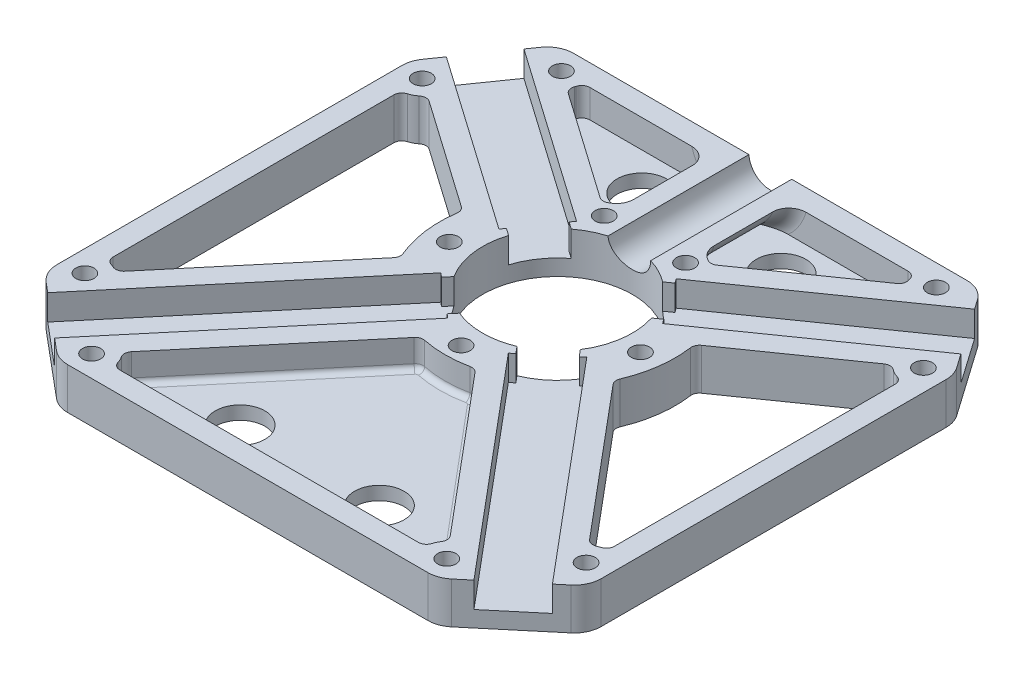
SolidWorks part; units mm, degrees
ref_plane "Front" through (0, 0, 0) normal (0, 0, 1) x (1, 0, 0)
ref_plane "Top" through (0, 0, 0) normal (0, 1, 0) x (1, 0, 0)
ref_plane "Right" through (0, 0, 0) normal (1, 0, 0) x (0, 0, -1)
sketch "Layout Sketch" plane through (0, 0, 0) normal (0, 1, 0) x (1, 0, 0)
  line L0 (0, 0) -> (0, 215) construction
  line L1 (0, 0) -> (-176.1177, 123.3189) construction
  line L2 (0, 0) -> (-138.1993, -164.6996) construction
  line L3 (-176.1177, 123.3189) -> (-12.2873, 8.6036)
  line L4 (-138.1993, -164.6996) -> (-9.6418, -11.4907)
  line L5 (138.1993, -164.6996) -> (9.6418, -11.4907)
  line L6 (176.1177, 123.3189) -> (12.2873, 8.6036)
  line L8 (-43.5, 110) -> (43.5, 110)
  line L9 (-43.5, 110) -> (-43.5, -70)
  line L10 (-43.5, -70) -> (43.5, -70)
  line L11 (43.5, 110) -> (43.5, -70)
  line L12 (-43.5, 110) -> (43.5, -70) construction
  line L13 (-43.5, -70) -> (43.5, 110) construction
  circle A0 centre (0, 0) radius 215
  circle A1 centre (0, 0) radius 15
  circle A2 centre (-176.1177, 123.3189) radius 127
  circle A3 centre (-138.1993, -164.6996) radius 127
  circle A4 centre (138.1993, -164.6996) radius 127
  circle A5 centre (176.1177, 123.3189) radius 127
  point P17 (0, 20)
  dimension "D3" = 30
  dimension "D5" = 430
  dimension "D6" = 254
  dimension "D1" = 55
  dimension "D2" = 40
  dimension "D4" = 200
  dimension "D7" = 87
  dimension "D8" = 70
  dimension "D9" = 180
ref_plane "Plane1" through (12.2873, 0, -8.6036) normal (-0.8192, 0, 0.5736) x (0.5736, 0, 0.8192)
sketch "Sketch2" plane through (12.2873, 0, -8.6036) normal (-0.8192, 0, 0.5736) x (0.5736, 0, 0.8192)
  line L1 (-5, -5) -> (5, -5)
  line L2 (-5, -5) -> (-5, 5)
  line L3 (-5, 5) -> (5, 5)
  line L4 (5, -5) -> (5, 5)
  line L5 (-5, -5) -> (5, 5) construction
  line L6 (-5, 5) -> (5, -5) construction
  circle A0 centre (0, 0) radius 4
  dimension "D2" = 8
  dimension "D1" = 10
extrude "Boss-Extrude2" add sketch "Sketch2" against normal up to vertex (200 mm away) contours L3 L4 L1 L2 up to point (176.1177, 0, -123.3189)
ref_plane "Plane2" through (9.6418, 0, 11.4907) normal (-0.6428, 0, -0.766) x (-0.766, 0, 0.6428)
sketch "Sketch4" plane through (9.6418, 0, 11.4907) normal (-0.6428, 0, -0.766) x (-0.766, 0, 0.6428)
  line B0 (-5, -5) -> (5, -5)
  line B1 (-5, -5) -> (-5, 5)
  line B2 (-5, 5) -> (5, 5)
  line B3 (5, -5) -> (5, 5)
  circle B4 centre (0, 0) radius 4
sketch_block_instance "Block-10mm Carbon-1"
sketch_block "Block-10mm Carbon" parameters "D2"=8, "D1"=10
extrude "Boss-Extrude1" add sketch "Sketch4" against normal up to vertex (200 mm away) separate body up to point (138.1993, 0, 164.6996)
mirror "Mirror1" about plane through (0, 0, 0) normal (1, 0, 0) of bodies 103 102
sketch "Sketch5" plane through (0, -5, 0) normal (0, -1, 0) x (1, 0, 0)
  line L0 (-39.3176, -39.7382) -> (39.3176, -39.7382)
  line L1 (39.3176, -39.7382) -> (50.7891, -23.3552)
  line L2 (50.7891, -23.3552) -> (50.7891, 44.9709)
  line L3 (50.7891, 44.9709) -> (35.4682, 57.8266)
  line L4 (35.4682, 57.8266) -> (-35.4682, 57.8266)
  line L5 (0, 57.8266) -> (0, -39.7382) construction
  line L6 (-39.3176, -39.7382) -> (-50.7891, -23.3552)
  line L7 (-50.7891, -23.3552) -> (-50.7891, 44.9709)
  line L8 (-50.7891, 44.9709) -> (-35.4682, 57.8266)
  line L9 (9.6418, 11.4907) -> (138.1993, 164.6996) construction
  line L10 (13.472, 8.2767) -> (5.8116, 14.7046) construction
  line L11 (142.0296, 161.4856) -> (134.3691, 167.9135) construction
  line L12 (12.2873, -8.6036) -> (176.1177, -123.3189) construction
  line L13 (9.4194, -12.6994) -> (15.1552, -4.5079) construction
  line L14 (173.2498, -127.4147) -> (178.9856, -119.2232) construction
  point P23 (45.0534, -31.5467)
  point P24 (43.1287, 51.3988)
  dimension "D1" = 20
  dimension "D2" = 40
  dimension "D3" = 101.5783
extrude "Boss-Extrude3" add sketch "Sketch5" along normal blind 3 and the other way blind 4.75 separate body
sketch "Sketch7" plane through (0, -5, 0) normal (0, -1, 0) x (1, 0, 0)
  line L0 (5.6584, 14.8332) -> (39.1453, 54.7413)
  line L1 (5.6584, 14.8332) -> (13.6252, 8.1482)
  line L2 (39.1453, 54.7413) -> (47.1121, 48.0563)
  line L3 (42.0708, -35.8063) -> (9.3047, -12.8632)
  line L4 (42.0708, -35.8063) -> (48.036, -27.2871)
  line L5 (9.3047, -12.8632) -> (15.2699, -4.3441)
  line L6 (48.036, -27.2871) -> (15.2699, -4.3441)
  line L7 (42.0708, -35.8063) -> (15.2699, -4.3441) construction
  line L8 (9.3047, -12.8632) -> (48.036, -27.2871) construction
  line L9 (9.4194, -12.6994) -> (15.1552, -4.5079) construction
  line L10 (176.1177, -123.3189) -> (12.2873, -8.6036) construction
  line L11 (173.2498, -127.4147) -> (178.9856, -119.2232) construction
  line L12 (39.3176, -39.7382) -> (50.7891, -23.3552) construction
  line L13 (173.2498, -127.4147) -> (9.4194, -12.6994) construction
  line L14 (9.6418, 11.4907) -> (138.1993, 164.6996) construction
  line L15 (5.8116, 14.7046) -> (13.472, 8.2767) construction
  line L16 (134.3691, 167.9135) -> (142.0296, 161.4856) construction
  line L17 (13.6252, 8.1482) -> (47.1121, 48.0563)
  line L18 (5.6584, 14.8332) -> (47.1121, 48.0563) construction
  line L19 (39.1453, 54.7413) -> (13.6252, 8.1482) construction
  line L20 (50.7891, 44.9709) -> (35.4682, 57.8266) construction
  line L21 (142.0296, 161.4856) -> (13.472, 8.2767) construction
  line L22 (0, 0) -> (0, 57.8266) construction
  line L23 (35.4682, 57.8266) -> (-35.4682, 57.8266) construction
  line L24 (-39.1453, 54.7413) -> (-47.1121, 48.0563)
  line L25 (-5.6584, 14.8332) -> (-39.1453, 54.7413)
  line L26 (-13.6252, 8.1482) -> (-47.1121, 48.0563)
  line L27 (-5.6584, 14.8332) -> (-13.6252, 8.1482)
  line L28 (-48.036, -27.2871) -> (-15.2699, -4.3441)
  line L29 (-42.0708, -35.8063) -> (-48.036, -27.2871)
  line L30 (-42.0708, -35.8063) -> (-9.3047, -12.8632)
  line L31 (-9.3047, -12.8632) -> (-15.2699, -4.3441)
  point P5 (28.6703, -20.0752)
  point P22 (26.3852, 31.4447)
  dimension "D1" = 0.2
  dimension "D2" = 0.2
extrude "Cut-Extrude1" cut sketch "Sketch7" against normal through all
sketch "Sketch8" plane through (0, -0.25, 0) normal (0, 1, 0) x (1, 0, 0)
  line L0 (-9.8783, 12.0441) -> (-8.5309, 11.1006)
  line L1 (-9.3047, 12.8632) -> (-15.2699, 4.3441) construction
  line L2 (-14.6963, 5.1632) -> (-13.3489, 4.2198)
  line L3 (-9.3047, 12.8632) -> (-15.2699, 4.3441) construction
  line L4 (-12.8592, -8.791) -> (-11.8019, -7.5309)
  line L5 (-13.6252, -8.1482) -> (-5.6584, -14.8332) construction
  line L6 (-6.4244, -14.1904) -> (-5.3671, -12.9303)
  line L7 (-13.6252, -8.1482) -> (-5.6584, -14.8332) construction
  line L8 (-5.6584, -14.8332) -> (-39.1453, -54.7413) construction
  line L9 (-47.1121, -48.0563) -> (-13.6252, -8.1482) construction
  line L10 (-15.2699, 4.3441) -> (-48.036, 27.2871) construction
  line L11 (-42.0708, 35.8063) -> (-9.3047, 12.8632) construction
  line L12 (0, 0) -> (0, 39.7382) construction
  line L13 (-39.3176, 39.7382) -> (39.3176, 39.7382) construction
  line L14 (6.4244, -14.1904) -> (5.3671, -12.9303)
  line L15 (12.8592, -8.791) -> (11.8019, -7.5309)
  line L16 (14.6963, 5.1632) -> (13.3489, 4.2198)
  line L17 (9.8783, 12.0441) -> (8.5309, 11.1006)
  line L18 (15.2699, 4.3441) -> (9.3047, 12.8632) construction
  line L19 (5.6584, -14.8332) -> (13.6252, -8.1482) construction
  line L20 (14.6963, 5.1632) -> (9.8783, 12.0441)
  line L21 (-9.8783, 12.0441) -> (-14.6963, 5.1632)
  line L22 (-12.8592, -8.791) -> (-6.4244, -14.1904)
  line L23 (6.4244, -14.1904) -> (12.8592, -8.791)
  arc A0 (-13.3489, 4.2198) -> (-11.8019, -7.5309) centre (0, 0) ccw
  arc A1 (-5.3671, -12.9303) -> (5.3671, -12.9303) centre (0, 0) ccw
  arc A2 (11.8019, -7.5309) -> (13.3489, 4.2198) centre (0, 0) ccw
  arc A3 (8.5309, 11.1006) -> (-8.5309, 11.1006) centre (0, 0) ccw
  dimension "D5" = 28
  dimension "D1" = 1
  dimension "D2" = 1
  dimension "D3" = 1
  dimension "D4" = 1
extrude "Cut-Extrude2" cut sketch "Sketch8" against normal up to surface (4.75 mm away) up to face at (28.6703, -5, -20.0752)
sketch "Sketch14" plane through (0, -0.25, 0) normal (0, 1, 0) x (1, 0, 0)
  line L0 (17.9502, 1.3378) -> (43.5125, 19.2367)
  line L1 (46.7891, 17.531) -> (46.7891, -37.4485)
  line L2 (44.218, -38.3843) -> (16.9923, -5.938)
  line L3 (2.8971, -17.7653) -> (30.585, -50.7625)
  line L4 (31.7232, 33.4439) -> (7.3964, 16.4102)
  line L27 (7.3964, 16.4102) -> (34.9998, 35.7382)
  line L28 (34.9998, 35.7382) -> (-34.9998, 35.7382)
  line L29 (-34.9998, 35.7382) -> (-7.3964, 16.4102)
  line L31 (30.9998, 35.7382) -> (-30.9998, 35.7382)
  line L32 (-31.7232, 33.4439) -> (-7.3964, 16.4102)
  line L33 (-17.9502, 1.3378) -> (-46.7891, 21.531)
  line L34 (-46.7891, 21.531) -> (-46.7891, -41.4485)
  line L35 (-46.7891, -41.4485) -> (-16.9923, -5.938)
  line L36 (-17.9502, 1.3378) -> (-43.5125, 19.2367)
  line L37 (-46.7891, 17.531) -> (-46.7891, -37.4485)
  line L38 (-44.218, -38.3843) -> (-16.9923, -5.938)
  line L39 (0, 0) -> (0, 39.7382) construction
  line L40 (-39.3176, 39.7382) -> (39.3176, 39.7382) construction
  line L41 (0, 0) -> (0, -57.8266) construction
  line L42 (35.4682, -57.8266) -> (-35.4682, -57.8266) construction
  line L48 (-2.8971, -17.7653) -> (-33.1562, -53.8266)
  line L49 (-33.1562, -53.8266) -> (33.1562, -53.8266)
  line L50 (33.1562, -53.8266) -> (2.8971, -17.7653)
  line L51 (-2.8971, -17.7653) -> (-30.585, -50.7625)
  line L52 (-29.1562, -53.8266) -> (29.1562, -53.8266)
  arc A0 (17.9502, 1.3378) -> (16.9923, -5.938) centre (0, 0) cw
  arc A1 (46.7891, 17.531) -> (43.5125, 19.2367) centre (46.7891, 21.531) cw
  arc A2 (44.218, -38.3843) -> (46.7891, -37.4485) centre (46.7891, -41.4485) cw
  arc A3 (7.3964, 16.4102) -> (-7.3964, 16.4102) centre (0, 0) ccw
  arc A4 (7.3964, 16.4102) -> (-7.3964, 16.4102) centre (0, 0) ccw
  arc A5 (-17.9502, 1.3378) -> (-16.9923, -5.938) centre (0, 0) ccw
  arc A6 (-17.9502, 1.3378) -> (-16.9923, -5.938) centre (0, 0) ccw
  arc A7 (-44.218, -38.3843) -> (-46.7891, -37.4485) centre (-46.7891, -41.4485) ccw
  arc A8 (-2.8971, -17.7653) -> (2.8971, -17.7653) centre (0, 0) ccw
  arc A9 (-2.8971, -17.7653) -> (2.8971, -17.7653) centre (0, 0) ccw
  arc A10 (-46.7891, 17.531) -> (-43.5125, 19.2367) centre (-46.7891, 21.531) ccw
  arc A11 (-31.7232, 33.4439) -> (-30.9998, 35.7382) centre (-34.9998, 35.7382) ccw
  arc A12 (-29.1562, -53.8266) -> (-30.585, -50.7625) centre (-33.1562, -53.8266) ccw
  arc A13 (29.1562, -53.8266) -> (30.585, -50.7625) centre (33.1562, -53.8266) cw
  arc A14 (31.7232, 33.4439) -> (30.9998, 35.7382) centre (34.9998, 35.7382) cw
  point P42 (0, -53.8266)
  point P43 (0, 35.7382)
  dimension "D4" = 8
  dimension "D1" = 4
  dimension "D2" = 4
  dimension "D3" = 4
extrude "Cut-Extrude4" cut sketch "Sketch14" against normal offset from surface (5.25 mm away) 2.5 up to face at (0, -8, 9.926)
other "Move Face1" face at (17.6586, -2.875, 2.3248) face at (-17.6586, -2.875, 2.3248) offset 4 parameters "D1"=4
sketch "Sketch15" plane through (0, -0.25, 0) normal (0, 1, 0) x (1, 0, 0)
  line L0 (-44.218, -38.3843) -> (-19.8931, -9.395) construction
  line L1 (-21.6468, 3.9261) -> (-43.5125, 19.2367) construction
  line L3 (-31.7232, 33.4439) -> (-7.3964, 16.4102) construction
  line L4 (7.3964, 16.4102) -> (31.7232, 33.4439) construction
  line L7 (30.585, -50.7625) -> (2.8971, -17.7653) construction
  line L8 (-2.8971, -17.7653) -> (-30.585, -50.7625) construction
  line L9 (19.8931, -9.395) -> (44.218, -38.3843) construction
  line L11 (43.5125, 19.2367) -> (21.6468, 3.9261) construction
  line L12 (-19.1818, -8.5474) -> (-19.8931, -9.395)
  line L13 (-21.6468, 3.9261) -> (-20.7404, 3.2915)
  line L15 (-10.1866, 18.3639) -> (-7.3964, 16.4102)
  line L16 (7.3964, 16.4102) -> (10.1866, 18.3639)
  line L19 (5.0866, -20.3746) -> (2.8971, -17.7653)
  line L20 (-2.8971, -17.7653) -> (-5.0866, -20.3746)
  line L21 (19.8931, -9.395) -> (19.1818, -8.5474)
  line L23 (20.7404, 3.2915) -> (21.6468, 3.9261)
  arc A0 (-20.7404, 3.2915) -> (-19.1818, -8.5474) centre (0, 0) ccw
  arc A2 (8.5309, 11.1006) -> (-8.5309, 11.1006) centre (0, 0) ccw construction
  arc A4 (-21.6468, 3.9261) -> (-19.8931, -9.395) centre (0, 0) ccw construction
  arc A7 (7.3964, 16.4102) -> (-7.3964, 16.4102) centre (0, 0) ccw construction
  arc A11 (-2.8971, -17.7653) -> (2.8971, -17.7653) centre (0, 0) ccw construction
  arc A12 (19.8931, -9.395) -> (21.6468, 3.9261) centre (0, 0) ccw construction
  arc A16 (-21.6468, 3.9261) -> (-19.8931, -9.395) centre (0, 0) ccw
  arc A19 (7.3964, 16.4102) -> (-7.3964, 16.4102) centre (0, 0) ccw
  arc A23 (-2.8971, -17.7653) -> (2.8971, -17.7653) centre (0, 0) ccw
  arc A24 (19.8931, -9.395) -> (21.6468, 3.9261) centre (0, 0) ccw
  arc A27 (10.1866, 18.3639) -> (-10.1866, 18.3639) centre (0, 0) ccw
  arc A28 (19.1818, -8.5474) -> (20.7404, 3.2915) centre (0, 0) ccw
  arc A29 (-5.0866, -20.3746) -> (5.0866, -20.3746) centre (0, 0) ccw
  dimension "D1" = 7
extrude "Boss-Extrude7" add sketch "Sketch15" against normal up to surface (5.25 mm away) up to face at (-37.2665, -5.5, 7.4742)
sketch "Sketch10" plane through (0, 0, -39.7382) normal (0, 0, 1) x (1, 0, 0)
  line L2 (7.5, -0.25) -> (-7.5, -0.25)
  line L3 (35.4682, -0.25) -> (-35.4682, -0.25) construction
  line L4 (0, -0.25) -> (0, 2.875) construction
  arc A0 (-7.5, -0.25) -> (7.5, -0.25) centre (0, 2.875) ccw
  point P4 (-7.5, -0.25)
  point P6 (7.5, -0.25)
  point P12 (0, -5.25)
  dimension "D1" = 15
  dimension "D2" = 5
extrude "Boss-Extrude8" add sketch "Sketch10" along normal up to surface (20.1232 mm away) up to face at (0, -2.875, -19.6819)
sketch "Sketch11" plane through (0, 0, -39.7382) normal (0, 0, -1) x (-1, 0, 0)
  circle A0 centre (0, 0) radius 4
  dimension "D1" = 8
extrude "Cut-Extrude3" cut sketch "Sketch11" against normal up to surface (26.3218 mm away) up to face at (0, -2.625, -12.5503)
hole_wizard "M3 Clearance Hole2" positions "Sketch17" profile "Sketch16" hole size "M3" standard "ANSI Metric" end condition through all
sketch "Sketch17" plane through (0, -0.25, 0) normal (0, 1, 0) x (1, 0, 0)
  line L0 (-21.8118, -2.8716) -> (-13.8802, -1.8274) construction
  line L1 (-10.1866, 18.3639) -> (-7.5, 19.615) construction
  line L4 (-8.8433, 18.9895) -> (-5.9103, 12.6913) construction
  line L7 (0, 0) -> (0, 33.2482) construction
  line L10 (8.8433, 18.9895) -> (5.9103, 12.6913) construction
  circle A0 centre (0, 0) radius 18
  arc A2 (-13.3489, 4.2198) -> (-11.8019, -7.5309) centre (0, 0) ccw construction
  arc A3 (-3.9922, 13.4187) -> (-8.5309, 11.1006) centre (0, 0) ccw construction
  arc A4 (-21.6468, 3.9261) -> (-19.8931, -9.395) centre (0, 0) ccw construction
  point P18 (-46.7891, 21.531)
  point P21 (-34.9998, 35.7382)
  point P24 (-46.7891, -41.4485)
  point P27 (-33.1562, -53.8266)
  point P30 (0, -18)
  point P33 (-17.846, -2.3495)
  point P34 (-7.5989, 16.3174)
  point P60 (33.1562, -53.8266)
  point P63 (17.846, -2.3495)
  point P64 (46.7891, -41.4485)
  point P65 (46.7891, 21.531)
  point P66 (34.9998, 35.7382)
  point P67 (7.5989, 16.3174)
sketch "Sketch16" plane through (-46.7891, -0.25, -21.531) normal (1, 0, 0) x (0, 0, 1)
  line L0 (0, 0) -> (0, 7.75)
  line L1 (0, 7.75) -> (1.7, 7.75)
  line L2 (1.7, 7.75) -> (1.7, 0)
  line L5 (1.7, 0) -> (0, 0)
  line L11 (0, -6.35) -> (0, 107.95) construction
  dimension "Thru Hole Dia." = 3.4
  dimension "Thru Hole Depth" = 7.75
fillet "Fillet1" radius 1.5 24 edges at (46.7891, -2.875, 37.4485) (44.218, -2.875, 38.3843) (-10.1866, -2.875, -18.3639) (10.1866, -2.875, -18.3639) (43.5125, -2.875, -19.2367) (46.7891, -2.875, -17.531) (30.9998, -2.875, -35.7382) (31.7232, -2.875, -33.4439) (-31.7232, -2.875, -33.4439) (-30.9998, -2.875, -35.7382) (29.1562, -2.875, 53.8266) (30.585, -2.875, 50.7625) (5.0866, -2.875, 20.3746) (-5.0866, -2.875, 20.3746) (-29.1562, -2.875, 53.8266) (-30.585, -2.875, 50.7625) (-46.7891, -2.875, 37.4485) (-44.218, -2.875, 38.3843) (-46.7891, -2.875, -17.531) (-43.5125, -2.875, -19.2367) (21.6468, -2.875, -3.9261) (19.8931, -2.875, 9.395) (-19.8931, -2.875, 9.395) (-21.6468, -2.875, -3.9261)
sketch "Sketch18" plane through (0, -5.5, 0) normal (0, 1, 0) x (1, 0, 0)
  line L3 (-46.7891, 16.2395) -> (-46.7891, -36.1569)
  line L4 (-43.3878, -37.3949) -> (-20.4965, -10.1141)
  line L5 (-22.4158, 4.4646) -> (-42.4546, 18.4959)
  line L6 (-46.7891, 16.2395) -> (-46.7891, -36.1569)
  line L7 (-43.3878, -37.3949) -> (-20.4965, -10.1141)
  line L8 (-22.4158, 4.4646) -> (-42.4546, 18.4959)
  line L9 (46.7891, -36.1569) -> (46.7891, 16.2395)
  line L10 (42.4546, 18.4959) -> (22.4158, 4.4646)
  line L11 (20.4965, -10.1141) -> (43.3878, -37.3949)
  line L12 (46.7891, -36.1569) -> (46.7891, 16.2395)
  line L13 (42.4546, 18.4959) -> (22.4158, 4.4646)
  line L14 (20.4965, -10.1141) -> (43.3878, -37.3949)
  arc A7 (-21.7904, 3.0293) -> (-20.2639, -8.5659) centre (0, 0) ccw
  arc A8 (-21.7904, 3.0293) -> (-20.2639, -8.5659) centre (0, 0) ccw
  arc A9 (-46.7891, -36.1569) -> (-45.6982, -37.6001) centre (-45.2891, -36.1569) ccw
  arc A10 (-45.1511, -37.7992) -> (-45.6982, -37.6001) centre (-46.7891, -41.4485) ccw
  arc A11 (-45.1511, -37.7992) -> (-43.3878, -37.3949) centre (-44.5369, -36.4307) ccw
  arc A12 (20.2639, -8.5659) -> (21.7904, 3.0293) centre (0, 0) ccw
  arc A13 (20.2639, -8.5659) -> (21.7904, 3.0293) centre (0, 0) ccw
  arc A15 (-42.4546, 18.4959) -> (-44.2625, 18.43) centre (-43.3149, 17.2672) ccw
  arc A16 (-45.6982, 17.6826) -> (-44.2625, 18.43) centre (-46.7891, 21.531) ccw
  arc A17 (-45.6982, 17.6826) -> (-46.7891, 16.2395) centre (-45.2891, 16.2395) ccw
  arc A18 (-46.7891, -36.1569) -> (-45.6982, -37.6001) centre (-45.2891, -36.1569) ccw
  arc A19 (-45.1511, -37.7992) -> (-45.6982, -37.6001) centre (-46.7891, -41.4485) ccw
  arc A20 (-45.1511, -37.7992) -> (-43.3878, -37.3949) centre (-44.5369, -36.4307) ccw
  arc A22 (-20.4965, -10.1141) -> (-20.2639, -8.5659) centre (-21.6455, -9.1499) ccw
  arc A23 (-20.4965, -10.1141) -> (-20.2639, -8.5659) centre (-21.6455, -9.1499) ccw
  arc A24 (-42.4546, 18.4959) -> (-44.2625, 18.43) centre (-43.3149, 17.2672) ccw
  arc A25 (-45.6982, 17.6826) -> (-44.2625, 18.43) centre (-46.7891, 21.531) ccw
  arc A26 (-45.6982, 17.6826) -> (-46.7891, 16.2395) centre (-45.2891, 16.2395) ccw
  arc A27 (45.6982, -37.6001) -> (45.1511, -37.7992) centre (46.7891, -41.4485) ccw
  arc A28 (45.6982, -37.6001) -> (46.7891, -36.1569) centre (45.2891, -36.1569) ccw
  arc A29 (46.7891, 16.2395) -> (45.6982, 17.6826) centre (45.2891, 16.2395) ccw
  arc A30 (44.2625, 18.43) -> (45.6982, 17.6826) centre (46.7891, 21.531) ccw
  arc A31 (44.2625, 18.43) -> (42.4546, 18.4959) centre (43.3149, 17.2672) ccw
  arc A32 (-21.7904, 3.0293) -> (-22.4158, 4.4646) centre (-23.2762, 3.2358) ccw
  arc A33 (-21.7904, 3.0293) -> (-22.4158, 4.4646) centre (-23.2762, 3.2358) ccw
  arc A34 (22.4158, 4.4646) -> (21.7904, 3.0293) centre (23.2762, 3.2358) ccw
  arc A35 (43.3878, -37.3949) -> (45.1511, -37.7992) centre (44.5369, -36.4307) ccw
  arc A36 (45.6982, -37.6001) -> (45.1511, -37.7992) centre (46.7891, -41.4485) ccw
  arc A37 (45.6982, -37.6001) -> (46.7891, -36.1569) centre (45.2891, -36.1569) ccw
  arc A38 (46.7891, 16.2395) -> (45.6982, 17.6826) centre (45.2891, 16.2395) ccw
  arc A39 (44.2625, 18.43) -> (45.6982, 17.6826) centre (46.7891, 21.531) ccw
  arc A40 (44.2625, 18.43) -> (42.4546, 18.4959) centre (43.3149, 17.2672) ccw
  arc A41 (22.4158, 4.4646) -> (21.7904, 3.0293) centre (23.2762, 3.2358) ccw
  arc A42 (20.2639, -8.5659) -> (20.4965, -10.1141) centre (21.6455, -9.1499) ccw
  arc A43 (20.2639, -8.5659) -> (20.4965, -10.1141) centre (21.6455, -9.1499) ccw
  arc A44 (43.3878, -37.3949) -> (45.1511, -37.7992) centre (44.5369, -36.4307) ccw
  dimension "D1" = 0
  dimension "D2" = 0
extrude "Cut-Extrude5" cut sketch "Sketch18" against normal through all
fillet "Fillet2" radius 3 2 edges at (0, -5.25, -35.7382) (1.2093, -5.1595, -20.9652)
fillet "Fillet3" radius 1 12 edges at (-28.7692, -5.5, 53.5232) (-29.5309, -5.5, 52.1362) (-30.1038, -5.5, 50.6611) (-17.7149, -5.5, 35.4245) (-5.0192, -5.5, 20.6235) (0, -5.5, 21) (5.0192, -5.5, 20.6235) (17.7149, -5.5, 35.4245) (30.1038, -5.5, 50.6611) (29.5309, -5.5, 52.1362) (28.7692, -5.5, 53.5232) (0, -5.5, 53.8266) tangent propagation no
sketch "Sketch19" plane through (0, -5, 0) normal (0, 1, 0) x (1, 0, 0)
  circle A0 centre (0, 0) radius 14
  dimension "D1" = 28
extrude "Cut-Extrude6" cut sketch "Sketch19" against normal through all
fillet "Fillet5" radius 5 8 edges at (-35.4682, -4.125, 57.8266) (-50.7891, -4.125, 44.9709) (-50.7891, -4.125, -23.3552) (-39.3176, -4.125, -39.7382) (39.3176, -4.125, -39.7382) (50.7891, -4.125, -23.3552) (35.4682, -4.125, 57.8266) (50.7891, -4.125, 44.9709)
sketch "Sketch21" plane through (0, -8, 0) normal (0, -1, 0) x (1, 0, 0)
  line L0 (0, 0) -> (0, -39.7382) construction
  line L1 (4.7489, -17.9628) -> (7.5989, -19.6083)
  line L2 (7.5989, -19.6083) -> (10.4489, -17.9628)
  line L3 (10.4489, -17.9628) -> (10.4489, -14.6719)
  line L4 (10.4489, -14.6719) -> (7.5989, -13.0265)
  line L5 (7.5989, -13.0265) -> (4.7489, -14.6719)
  line L6 (4.7489, -14.6719) -> (4.7489, -17.9628)
  line L7 (31.7089, -35.7382) -> (33.3543, -38.5882)
  line L8 (33.3543, -38.5882) -> (36.6452, -38.5882)
  line L9 (36.6452, -38.5882) -> (38.2907, -35.7382)
  line L10 (38.2907, -35.7382) -> (36.6452, -32.8882)
  line L11 (36.6452, -32.8882) -> (33.3543, -32.8882)
  line L12 (33.3543, -32.8882) -> (31.7089, -35.7382)
  line L13 (43.9391, -23.1764) -> (46.7891, -24.8219)
  line L14 (46.7891, -24.8219) -> (49.6391, -23.1764)
  line L15 (49.6391, -23.1764) -> (49.6391, -19.8855)
  line L16 (49.6391, -19.8855) -> (46.7891, -18.2401)
  line L17 (46.7891, -18.2401) -> (43.9391, -19.8855)
  line L18 (43.9391, -19.8855) -> (43.9391, -23.1764)
  line L19 (-1.6454, 15.15) -> (1.6454, 15.15)
  line L20 (1.6454, 15.15) -> (3.2909, 18)
  line L21 (3.2909, 18) -> (1.6454, 20.85)
  line L22 (1.6454, 20.85) -> (-1.6454, 20.85)
  line L23 (-1.6454, 20.85) -> (-3.2909, 18)
  line L24 (-3.2909, 18) -> (-1.6454, 15.15)
  line L25 (20.696, 3.9949) -> (17.846, 5.6404)
  line L26 (17.846, 5.6404) -> (14.996, 3.9949)
  line L27 (14.996, 3.9949) -> (14.996, 0.704)
  line L28 (14.996, 0.704) -> (17.846, -0.9414)
  line L29 (17.846, -0.9414) -> (20.696, 0.704)
  line L30 (20.696, 0.704) -> (20.696, 3.9949)
  line L31 (48.4346, 44.2985) -> (45.1437, 44.2985)
  line L32 (45.1437, 44.2985) -> (43.4982, 41.4485)
  line L33 (43.4982, 41.4485) -> (45.1437, 38.5985)
  line L34 (45.1437, 38.5985) -> (48.4346, 38.5985)
  line L35 (48.4346, 38.5985) -> (50.08, 41.4485)
  line L36 (50.08, 41.4485) -> (48.4346, 44.2985)
  line L37 (31.5107, 56.6766) -> (29.8653, 53.8266)
  line L38 (29.8653, 53.8266) -> (31.5107, 50.9766)
  line L39 (31.5107, 50.9766) -> (34.8016, 50.9766)
  line L40 (34.8016, 50.9766) -> (36.4471, 53.8266)
  line L41 (36.4471, 53.8266) -> (34.8016, 56.6766)
  line L42 (34.8016, 56.6766) -> (31.5107, 56.6766)
  line L43 (-36.7148, -39.7382) -> (36.7148, -39.7382) construction
  line L44 (-34.8016, 56.6766) -> (-31.5107, 56.6766)
  line L45 (-36.4471, 53.8266) -> (-34.8016, 56.6766)
  line L46 (-34.8016, 50.9766) -> (-36.4471, 53.8266)
  line L47 (-31.5107, 50.9766) -> (-34.8016, 50.9766)
  line L48 (-29.8653, 53.8266) -> (-31.5107, 50.9766)
  line L49 (-31.5107, 56.6766) -> (-29.8653, 53.8266)
  line L50 (-50.08, 41.4485) -> (-48.4346, 44.2985)
  line L51 (-48.4346, 38.5985) -> (-50.08, 41.4485)
  line L52 (-45.1437, 38.5985) -> (-48.4346, 38.5985)
  line L53 (-43.4982, 41.4485) -> (-45.1437, 38.5985)
  line L54 (-45.1437, 44.2985) -> (-43.4982, 41.4485)
  line L55 (-48.4346, 44.2985) -> (-45.1437, 44.2985)
  line L56 (-20.696, 0.704) -> (-20.696, 3.9949)
  line L57 (-17.846, -0.9414) -> (-20.696, 0.704)
  line L58 (-14.996, 0.704) -> (-17.846, -0.9414)
  line L59 (-14.996, 3.9949) -> (-14.996, 0.704)
  line L60 (-17.846, 5.6404) -> (-14.996, 3.9949)
  line L61 (-20.696, 3.9949) -> (-17.846, 5.6404)
  line L62 (-43.9391, -19.8855) -> (-43.9391, -23.1764)
  line L63 (-46.7891, -18.2401) -> (-43.9391, -19.8855)
  line L64 (-49.6391, -19.8855) -> (-46.7891, -18.2401)
  line L65 (-49.6391, -23.1764) -> (-49.6391, -19.8855)
  line L66 (-46.7891, -24.8219) -> (-49.6391, -23.1764)
  line L67 (-43.9391, -23.1764) -> (-46.7891, -24.8219)
  line L68 (-33.3543, -32.8882) -> (-31.7089, -35.7382)
  line L69 (-36.6452, -32.8882) -> (-33.3543, -32.8882)
  line L70 (-38.2907, -35.7382) -> (-36.6452, -32.8882)
  line L71 (-36.6452, -38.5882) -> (-38.2907, -35.7382)
  line L72 (-33.3543, -38.5882) -> (-36.6452, -38.5882)
  line L73 (-31.7089, -35.7382) -> (-33.3543, -38.5882)
  line L74 (-4.7489, -14.6719) -> (-4.7489, -17.9628)
  line L75 (-7.5989, -13.0265) -> (-4.7489, -14.6719)
  line L76 (-10.4489, -14.6719) -> (-7.5989, -13.0265)
  line L77 (-10.4489, -17.9628) -> (-10.4489, -14.6719)
  line L78 (-7.5989, -19.6083) -> (-10.4489, -17.9628)
  line L79 (-4.7489, -17.9628) -> (-7.5989, -19.6083)
  circle A0 centre (7.5989, -16.3174) radius 2.85 construction
  circle A1 centre (34.9998, -35.7382) radius 2.85 construction
  circle A2 centre (46.7891, -21.531) radius 2.85 construction
  circle A3 centre (0, 18) radius 2.85 construction
  circle A4 centre (17.846, 2.3495) radius 2.85 construction
  circle A5 centre (46.7891, 41.4485) radius 2.85 construction
  circle A6 centre (33.1562, 53.8266) radius 2.85 construction
  circle A7 centre (-33.1562, 53.8266) radius 2.85 construction
  circle A8 centre (-46.7891, 41.4485) radius 2.85 construction
  circle A9 centre (-17.846, 2.3495) radius 2.85 construction
  circle A10 centre (-46.7891, -21.531) radius 2.85 construction
  circle A11 centre (-34.9998, -35.7382) radius 2.85 construction
  circle A12 centre (-7.5989, -16.3174) radius 2.85 construction
  dimension "D1" = 5.7
extrude "Cut-Extrude8" [suppressed] cut sketch "Sketch21" against normal blind 2.5
sketch "Sketch22" plane through (0, -8, 0) normal (0, -1, 0) x (1, 0, 0)
  line L0 (0, 0) -> (0, 57.8266) construction
  line L1 (33.6484, 57.8266) -> (-33.6484, 57.8266) construction
  circle A0 centre (-33.1562, 53.8266) radius 3
  circle A1 centre (-46.7891, 41.4485) radius 3
  circle A2 centre (0, 18) radius 3
  circle A3 centre (-17.846, 2.3495) radius 3
  circle A4 centre (-7.5989, -16.3174) radius 3
  circle A5 centre (-34.9998, -35.7382) radius 3
  circle A6 centre (-46.7891, -21.531) radius 3
  circle A7 centre (7.5989, -16.3174) radius 3
  circle A8 centre (34.9998, -35.7382) radius 3
  circle A9 centre (46.7891, -21.531) radius 3
  circle A10 centre (17.846, 2.3495) radius 3
  circle A11 centre (46.7891, 41.4485) radius 3
  circle A12 centre (33.1562, 53.8266) radius 3
  dimension "D1" = 6
extrude "Cut-Extrude9" cut sketch "Sketch22" against normal blind 2
sketch "Sketch23" plane through (0, -8, 0) normal (0, -1, 0) x (1, 0, 0)
  line L1 (-13, -28.7382) -> (13, -28.7382) construction
  line L2 (-13, -28.7382) -> (-13, 46.2618) construction
  line L3 (-13, 46.2618) -> (13, 46.2618) construction
  line L4 (13, -28.7382) -> (13, 46.2618) construction
  line L5 (-13, -28.7382) -> (13, 46.2618) construction
  line L6 (-13, 46.2618) -> (13, -28.7382) construction
  line L7 (-36.7148, -39.7382) -> (36.7148, -39.7382) construction
  circle A0 centre (-13, 46.2618) radius 4.625
  circle A1 centre (13, 46.2618) radius 4.625
  circle A2 centre (13, -28.7382) radius 4.625
  circle A3 centre (-13, -28.7382) radius 4.625
  point P0 (0, 8.7618)
  dimension "D1" = 9.25
  dimension "D2" = 75
  dimension "D3" = 11
  dimension "D4" = 26
extrude "Cut-Extrude10" cut sketch "Sketch23" against normal through all
delete or keep bodies "Body-Delete1" type delete bodies bodies 103 102 104 105
